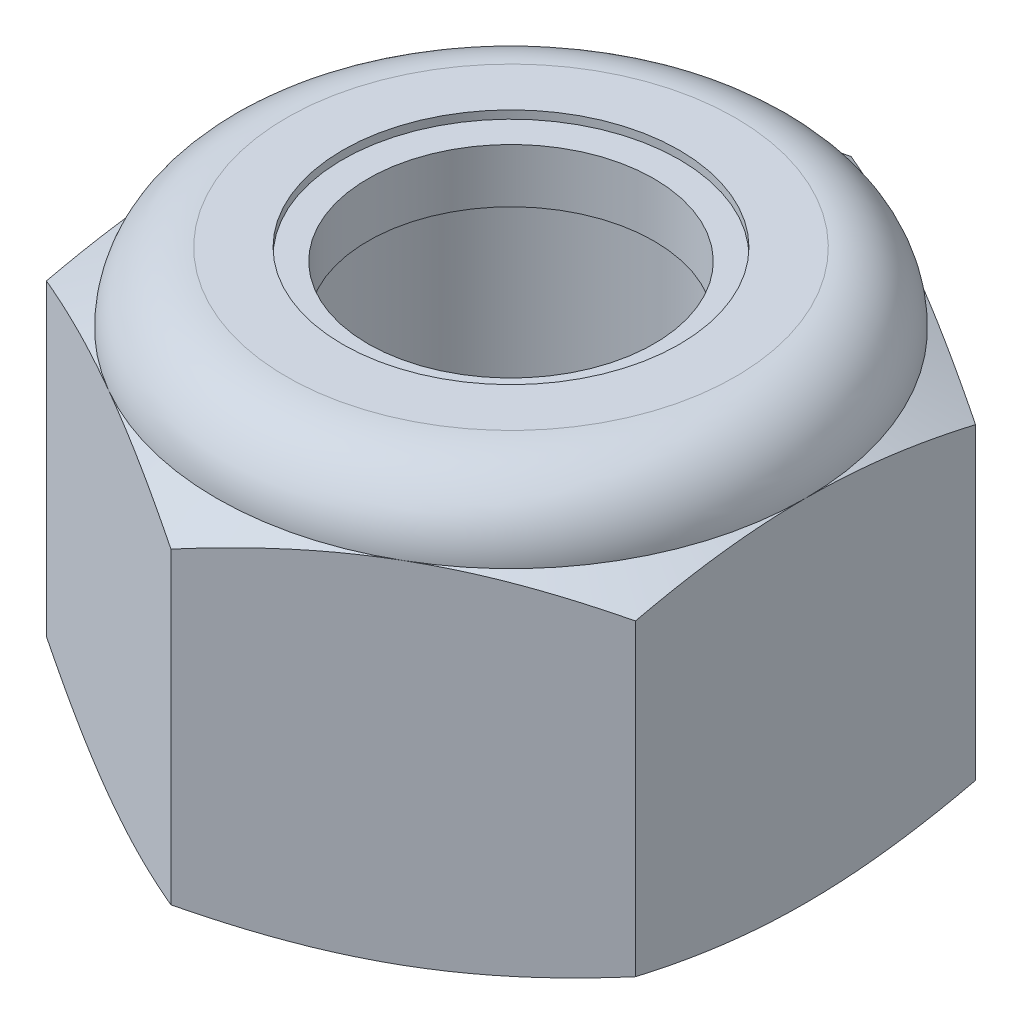
SolidWorks part; units mm, degrees
ref_plane "Front" through (0, 0, 0) normal (0, 0, 1) x (1, 0, 0)
ref_plane "Top" through (0, 0, 0) normal (0, 1, 0) x (1, 0, 0)
ref_plane "Right" through (0, 0, 0) normal (1, 0, 0) x (0, 0, -1)
sketch "Sketch8" plane through (0, 0, 0) normal (1, 0, 0) x (0, 0, -1)
  line L0 (0, 0) -> (0, 7.9375) construction
  line L1 (5.5562, 0) -> (-5.5562, 0) construction
  line L2 (-3.175, 7.9375) -> (3.175, 7.9375) construction
  line L3 (3.175, 7.9375) -> (3.175, 7.0304) construction
  point P7 (-2.6987, 7.9375)
  dimension "D1" = 5.3975
sketch "Sketch1" plane through (0, 0, 0) normal (0, 1, 0) x (1, 0, 0)
  line L1 (0, 6.4158) -> (-5.5563, 3.2079)
  line L2 (-5.5563, 3.2079) -> (-5.5562, -3.2079)
  line L3 (-5.5562, -3.2079) -> (0, -6.4158)
  line L4 (0, -6.4158) -> (5.5563, -3.2079)
  line L5 (5.5563, -3.2079) -> (5.5563, 3.2079)
  line L6 (5.5563, 3.2079) -> (0, 6.4158)
  circle A0 centre (0, 0) radius 5.5562 construction
  circle A1 centre (0, 0) radius 3.175
extrude "Extrude1" add sketch "Sketch1" along normal up to vertex (7.9375 mm away) up to point (0, 7.9375, 0)
sketch "Sketch5" plane through (0, 0, 0) normal (1, 0, 0) x (0, 0, -1)
  line L0 (0, 0) -> (5.5562, 0)
  line L1 (5.5562, 0) -> (6.4158, 0.4008)
  line L2 (6.4158, 0.4008) -> (6.4158, 6.2138)
  line L3 (6.4158, 6.2138) -> (5.5562, 6.6146)
  line L4 (4.2333, 7.9375) -> (4.2333, 9.2075)
  line L5 (4.2333, 9.2075) -> (7.6858, 9.2075)
  line L6 (7.6858, 9.2075) -> (7.6858, -1.27)
  line L7 (7.6858, -1.27) -> (0, -1.27)
  line L8 (0, -1.27) -> (0, 0)
  line L9 (5.5562, 6.6146) -> (5.5562, 0) construction
  line L12 (6.4158, 7.9375) -> (6.4158, 0) construction
  line L13 (6.4158, 3.9688) -> (7.6858, 3.9688) construction
  line L15 (0, 0) -> (0, 9.2075) construction
  line L18 (5.5562, 0) -> (-5.5562, 0) construction
  line L19 (3.2079, 7.9375) -> (6.4158, 7.9375) construction
  line L20 (0, 9.2075) -> (4.2333, 9.2075) construction
  line L21 (3.2079, 0) -> (6.4158, 0) construction
  arc A0 (5.5562, 6.6146) -> (4.2333, 7.9375) centre (4.2333, 6.6146) ccw
  dimension "D1" = 25
  dimension "D2" = 1.27
  dimension "D4" = 1.3229
revolve "Cut-Revolve3" cut sketch "Sketch5" angle 360 about L15
sketch "Sketch4" plane through (0, 0, 0) normal (1, 0, 0) x (0, 0, -1)
  line L0 (0, 6.6146) -> (3.4925, 6.6146)
  line L1 (3.4925, 6.6146) -> (0, 4.986)
  line L3 (0, 1.6286) -> (3.4925, 0)
  line L4 (3.4925, 0) -> (0, 0)
  line L5 (0, 0) -> (0, 6.6146) construction
  line L10 (0, 0) -> (0, 7.9375) construction
  line L11 (0, 1.6286) -> (0, 0)
  line L12 (0, 6.6146) -> (0, 4.986)
  line L13 (4.8119, 6.6146) -> (0, 6.6146) construction
  dimension "D1" = 25
  dimension "D2" = 6.985
sketch "Sketch6" plane through (0, 0, 0) normal (1, 0, 0) x (0, 0, -1)
  line L0 (0, 6.6146) -> (5.4039, 6.6146)
  line L1 (4.2333, 7.7851) -> (2.1167, 7.7851)
  line L2 (0, 9.2075) -> (0, 6.6146)
  line L3 (2.1167, 9.2075) -> (0, 9.2075)
  line L4 (0, 9.2075) -> (4.2333, 9.2075) construction
  line L5 (0, 0) -> (0, 9.2075) construction
  line L6 (0, 9.2075) -> (0, 0) construction
  line L7 (2.1167, 7.7851) -> (2.1167, 9.2075)
  line L8 (4.2333, 7.9375) -> (4.2333, 7.7851) construction
  line L9 (2.1167, 7.7851) -> (0, 7.7851) construction
  line L10 (0, 7.7851) -> (0, 4.986) construction
  arc A0 (5.4039, 6.6146) -> (4.2333, 7.7851) centre (4.2333, 6.6146) ccw
  arc A1 (5.5562, 6.6146) -> (4.2333, 7.9375) centre (4.2333, 6.6146) ccw construction
  dimension "D1" = 0.1524
revolve "Cut-Revolve4" cut sketch "Sketch6" angle 360 about L6
revolve "Cut-Revolve2" cut sketch "Sketch4" angle 360 about L5
sketch "Sketch7" plane through (0, 0, 0) normal (1, 0, 0) x (0, 0, -1)
  line L0 (2.6988, 6.6908) -> (5.325, 6.6908)
  line L1 (4.2333, 7.7089) -> (2.6988, 7.7089)
  line L2 (2.6988, 7.7089) -> (2.6988, 6.6908)
  line L3 (2.6988, 6.6908) -> (0, 6.6908) construction
  line L4 (0, 6.6908) -> (0, 7.7089) construction
  line L5 (0, 7.7089) -> (2.6988, 7.7089) construction
  line L6 (2.6988, 6.6908) -> (2.6988, 6.6146) construction
  line L7 (0, 6.6146) -> (5.4039, 6.6146) construction
  line L8 (4.2333, 7.7089) -> (4.2333, 7.7851) construction
  arc A0 (5.325, 6.6908) -> (4.2333, 7.7089) centre (4.2333, 6.6146) ccw
  arc A2 (5.4039, 6.6146) -> (4.2333, 7.7851) centre (4.2333, 6.6146) ccw construction
  dimension "D1" = 0.0762
  dimension "D2" = 5.3975
revolve "Revolve2" add sketch "Sketch7" angle 360 about L4
sketch "Sketch2" [suppressed] plane through (0, 0, 0) normal (1, 0, 0) x (0, 0, -1)
  line L0 (-3.175, 0) -> (-3.175, 6.6146) construction
  line L1 (0, 0) -> (3.175, 0)
  line L2 (0, 0) -> (0, 6.6146)
  line L3 (0, 6.6146) -> (3.175, 6.6146)
  line L4 (3.175, 0) -> (3.175, 6.6146)
  line L6 (4.8119, 6.6146) -> (5.5562, 6.6146) construction
  line L7 (0, -3.175) -> (0, 0) construction
revolve "Revolve1" [suppressed] add sketch "Sketch2" angle 360 about L7
sketch "Sketch9" [suppressed] plane through (0, 0, 0) normal (1, 0, 0) x (0, 0, -1)
  line L0 (3.2732, 7.465) -> (3.2732, 6.5579) construction
  line L1 (3.2732, 6.5579) -> (2.4876, 7.0115) construction
  line L2 (2.4876, 7.0115) -> (3.2732, 7.465) construction
  line L3 (2.5858, 7.0682) -> (2.5858, 6.9548) construction
  line L4 (3.175, 7.4083) -> (3.175, 6.6146) construction
  line L5 (2.4876, 7.0115) -> (2.5858, 7.0115) construction
  line L6 (3.175, 7.0115) -> (3.2732, 7.0115) construction
  line L7 (3.2241, 7.0115) -> (3.2241, 7.4367) construction
  line L8 (3.2732, 6.5579) -> (3.2241, 7.4367)
  line L9 (3.2241, 7.4367) -> (2.5858, 7.0682)
  line L10 (2.5858, 7.0682) -> (2.5858, 6.9548)
  line L11 (2.5858, 6.9548) -> (3.2732, 6.5579)
  dimension "D1" = 0.9071
  dimension "D2" = 0.1134
sketch "Sketch10" [suppressed] plane through (0, 6.6146, 0) normal (0, 1, 0) x (1, 0, 0)
  circle A1 centre (0, 0) radius 3.175
  circle A2 centre (0, 0) radius 3.175
  dimension "D1" = 0
curve "Helix/Spiral1" [suppressed] pitch 0.9071 height 8.8446 turns 9.75
sweep "Cut-Sweep1" [suppressed] cut profiles "Sketch9" path "Helix/Spiral1"
sketch "Sketch11" [suppressed] plane through (0, 0, 0) normal (1, 0, 0) x (0, 0, -1)
  line L0 (0, 0) -> (0, 7.9375) construction
  line L1 (5.5562, 0) -> (-5.5562, 0) construction
  line L4 (0, 7.9375) -> (0, 0) construction
  line L5 (0, 3.9688) -> (3.175, 3.9688) construction
  line L6 (0, 0) -> (3.4925, 0)
  line L7 (0, 1.6286) -> (0, 0)
  line L8 (3.4925, 0) -> (0, 1.6286)
  dimension "D1" = 6.985
  dimension "D2" = 25
revolve "Revolve3" [suppressed] add sketch "Sketch11" angle 360 about L4
sketch "Sketch12" [suppressed] plane through (0, 0, 0) normal (1, 0, 0) x (0, 0, -1)
  line L0 (3.4925, 6.6146) -> (0, 6.6146)
  line L1 (0, 6.6146) -> (0, 0)
  line L2 (0, 0) -> (3.4925, 0)
  line L3 (5.5562, 0) -> (-5.5562, 0) construction
  line L4 (3.4925, 0) -> (3.4925, 6.6146)
  line L5 (-3.4925, 0) -> (3.4925, 0) construction
revolve "Revolve4" [suppressed] add sketch "Sketch12" angle 360 about L0
combine bodies "Combine1" [suppressed] bodies to combine 136 133
equation "\"D4@Sketch5\"=\"Height@Sketch8\"/6"
equation "\"D1@Sketch9\"=\"Thread Pitch@Sketch8\""
equation "\"D2@Sketch9\"=\"Thread Pitch@Sketch8\"/8"
equation "\"D4@Helix/Spiral1\"=\"Thread Pitch@Sketch8\""
equation "\"D3@Helix/Spiral1\"=\"Thread Pitch@Sketch8\"+\"Height@Sketch8\""
equation "\"D2@Sketch4\"=\"Thread Dia@Sketch8\"*1.1"
equation "\"D1@Sketch11\"=\"Thread Dia@Sketch8\"*1.1"
equation "\"D2@Sketch7\"=\"Thread Dia@Sketch8\"*.85"
equation "\"D1@Sketch8\"=\"Thread Dia@Sketch8\"*.85"
